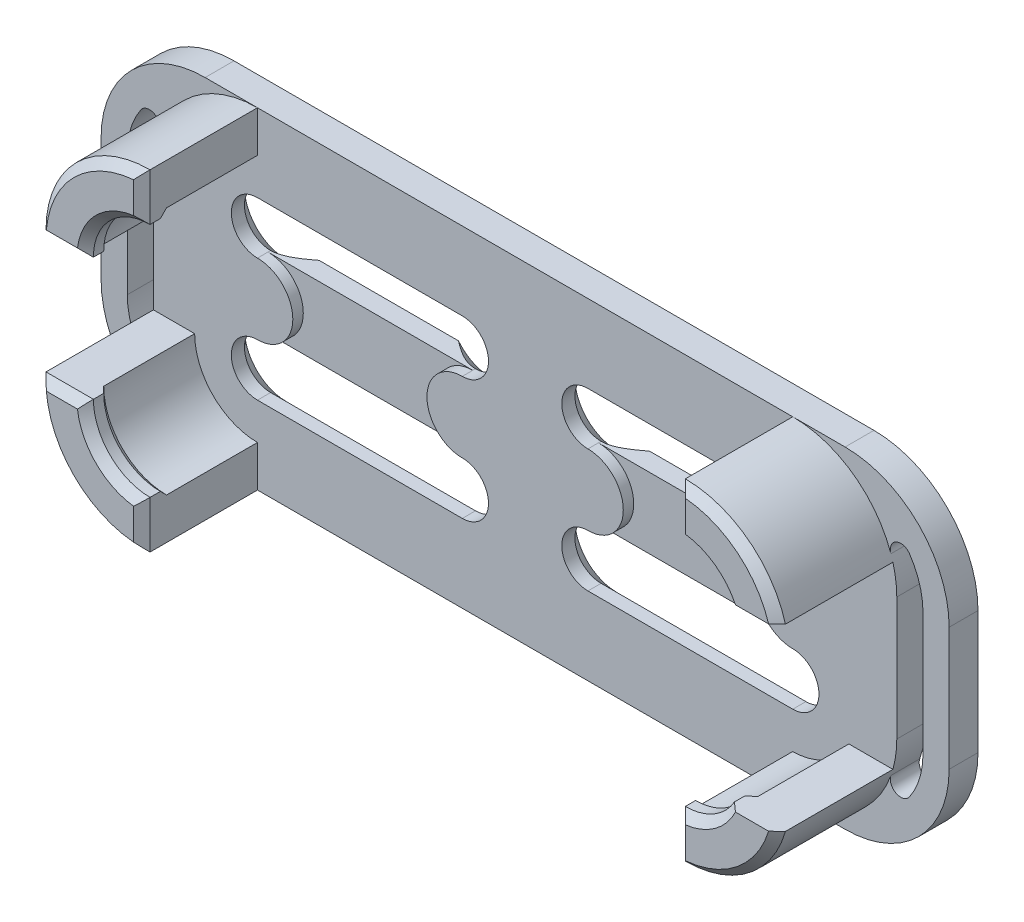
SolidWorks part; units mm, degrees
ref_plane "Front Plane" through (0, 0, 0) normal (0, 0, 1) x (1, 0, 0)
ref_plane "Top Plane" through (0, 0, 0) normal (0, 1, 0) x (1, 0, 0)
ref_plane "Right Plane" through (0, 0, 0) normal (1, 0, 0) x (0, 0, -1)
sketch "Sketch1" plane through (0, 0, 0) normal (0, 0, 1) x (1, 0, 0)
  line L0 (40.0844, 0) -> (-40.0844, 0) construction
  line L1 (0, -15.0813) -> (0, 15.0812) construction
  line L2 (40.0304, -8.8839) -> (60.6806, -8.8839)
  line L3 (60.6806, 8.8839) -> (40.0304, 8.8839)
  line L8 (-32.4644, -15.0813) -> (32.4644, -15.0812)
  line L9 (40.0844, -7.4612) -> (40.0844, 7.4612)
  line L10 (32.4644, 15.0812) -> (-32.4644, 15.0812)
  line L11 (-40.0844, 7.4612) -> (-40.0844, -7.4612)
  arc A8 (32.4644, -15.0812) -> (40.0844, -7.4612) centre (32.4644, -7.4612) ccw
  arc A9 (40.0844, 7.4612) -> (32.4644, 15.0812) centre (32.4644, 7.4612) ccw
  arc A10 (-32.4644, 15.0812) -> (-40.0844, 7.4612) centre (-32.4644, 7.4612) ccw
  arc A11 (-40.0844, -7.4612) -> (-32.4644, -15.0813) centre (-32.4644, -7.4612) ccw
  point P15 (0, 15.0812)
  point P18 (-40.0844, 0)
  point P22 (0, 0)
  point P25 (0, 0)
  point P27 (0, 0)
  point P29 (0, 0)
  dimension "D1" = 7.62
  dimension "D2" = 80.1688
  dimension "D3" = 30.1625
  dimension "D4" = 17.7678
sketch "Sketch2" plane through (0, 0, 0) normal (0, 0, 1) x (1, 0, 0)
  line L0 (-32.4644, 20.0813) -> (-32.4644, 15.0812)
  line L1 (-45.0844, 7.4612) -> (-40.0844, 7.4612)
  line L4 (-40.0844, 7.4612) -> (-40.0844, -7.4612)
  line L5 (32.4644, 15.0812) -> (-32.4644, 15.0813)
  line L6 (40.0844, -7.4612) -> (40.0844, 7.4612)
  line L7 (-32.4644, -15.0813) -> (32.4644, -15.0813)
  line L8 (-40.0844, 7.4612) -> (-40.0844, -7.4612) construction
  line L9 (32.4644, 15.0812) -> (-32.4644, 15.0813) construction
  line L10 (40.0844, -7.4612) -> (40.0844, 7.4612) construction
  line L11 (-32.4644, -15.0813) -> (32.4644, -15.0813) construction
  line L18 (32.4644, 20.0813) -> (32.4644, 15.0812)
  line L19 (45.0844, 7.4612) -> (40.0844, 7.4612)
  line L20 (-40.0844, -7.4612) -> (-45.0844, -7.4612)
  line L21 (-32.4644, -15.0813) -> (-32.4644, -20.0813)
  line L22 (32.4644, -20.0813) -> (32.4644, -15.0813)
  line L23 (40.0844, -7.4612) -> (45.0844, -7.4613)
  line L25 (32.4644, 20.0813) -> (-32.4644, 20.0813) construction
  line L26 (32.4644, 15.0812) -> (-32.4644, 15.0812) construction
  line L27 (45.0844, -7.4613) -> (45.0844, 7.4612) construction
  line L28 (40.0844, -7.4612) -> (40.0844, 7.4612) construction
  line L29 (-32.4644, -15.0813) -> (32.4644, -15.0813) construction
  line L30 (-32.4644, -20.0813) -> (32.4644, -20.0813) construction
  line L31 (-40.0844, 7.4612) -> (-40.0844, -7.4612) construction
  line L32 (-45.0844, 7.4612) -> (-45.0844, -7.4612) construction
  arc A0 (-40.0844, -7.4612) -> (-32.4644, -15.0813) centre (-32.4644, -7.4612) ccw
  arc A1 (32.4644, -15.0813) -> (40.0844, -7.4612) centre (32.4644, -7.4612) ccw
  arc A2 (40.0844, 7.4612) -> (32.4644, 15.0812) centre (32.4644, 7.4612) ccw
  arc A3 (-32.4644, 15.0812) -> (-40.0844, 7.4612) centre (-32.4644, 7.4612) ccw
  arc A4 (-32.4644, 15.0813) -> (-40.0844, 7.4612) centre (-32.4644, 7.4612) ccw
  arc A5 (40.0844, 7.4612) -> (32.4644, 15.0812) centre (32.4644, 7.4612) ccw
  arc A6 (32.4644, -15.0813) -> (40.0844, -7.4612) centre (32.4644, -7.4612) ccw
  arc A7 (-40.0844, -7.4612) -> (-32.4644, -15.0813) centre (-32.4644, -7.4612) ccw
  arc A8 (-32.4644, 15.0813) -> (-40.0844, 7.4612) centre (-32.4644, 7.4612) ccw construction
  arc A9 (40.0844, 7.4612) -> (32.4644, 15.0812) centre (32.4644, 7.4612) ccw construction
  arc A10 (32.4644, -15.0813) -> (40.0844, -7.4612) centre (32.4644, -7.4612) ccw construction
  arc A11 (-40.0844, -7.4612) -> (-32.4644, -15.0813) centre (-32.4644, -7.4612) ccw construction
  arc A12 (-45.0844, -7.4612) -> (-32.4644, -20.0813) centre (-32.4644, -7.4612) ccw
  arc A13 (32.4644, -20.0813) -> (45.0844, -7.4613) centre (32.4644, -7.4612) ccw
  arc A14 (45.0844, 7.4612) -> (32.4644, 20.0813) centre (32.4644, 7.4612) ccw
  arc A15 (-32.4644, 20.0813) -> (-45.0844, 7.4612) centre (-32.4644, 7.4612) ccw
  dimension "D1" = 0
  dimension "D3" = 5
extrude "Boss-Extrude1" add sketch "Sketch2" along normal blind 12.0331
sketch "Sketch3" plane through (0, 0, 0) normal (0, 0, -1) x (-1, 0, 0)
  line L0 (-45.0844, 7.4612) -> (-45.0844, -7.4612)
  line L1 (32.4644, -20.0813) -> (-32.4644, -20.0813)
  line L2 (45.0844, -7.4612) -> (45.0844, 7.4612)
  line L3 (32.4644, 20.0812) -> (-32.4644, 20.0813)
  line L4 (7.62, 7.4612) -> (32.4644, 7.4612) construction
  line L6 (7.62, 10.6362) -> (32.4644, 10.6362)
  line L7 (7.62, 4.2862) -> (32.4644, 4.2862)
  line L8 (-45.255, 0) -> (-50045.255, 0) construction
  line L9 (7.62, -7.4612) -> (32.4644, -7.4612) construction
  line L10 (7.62, -10.6362) -> (32.4644, -10.6362)
  line L11 (7.62, -4.2862) -> (32.4644, -4.2862)
  line L12 (35.6394, -7.4612) -> (40.0844, -7.4612) construction
  line L13 (4.445, -7.4612) -> (0, -7.4612) construction
  line L14 (0, -15.0813) -> (0, 15.0812) construction
  line L15 (0, 0) -> (0, 49794.0709) construction
  line L16 (-7.62, -7.4612) -> (-32.4644, -7.4612) construction
  line L17 (-7.62, -10.6362) -> (-32.4644, -10.6362)
  line L18 (-7.62, -4.2862) -> (-32.4644, -4.2862)
  line L19 (-7.62, 7.4612) -> (-32.4644, 7.4612) construction
  line L20 (-7.62, 10.6362) -> (-32.4644, 10.6362)
  line L21 (-7.62, 4.2862) -> (-32.4644, 4.2862)
  arc A0 (-45.0844, -7.4612) -> (-32.4644, -20.0813) centre (-32.4644, -7.4612) ccw construction
  arc A1 (32.4644, -20.0813) -> (45.0844, -7.4612) centre (32.4644, -7.4612) ccw construction
  arc A2 (45.0844, 7.4612) -> (32.4644, 20.0812) centre (32.4644, 7.4612) ccw construction
  arc A3 (-32.4644, 20.0813) -> (-45.0844, 7.4612) centre (-32.4644, 7.4612) ccw construction
  arc A4 (-45.0844, -7.4612) -> (-32.4644, -20.0813) centre (-32.4644, -7.4612) ccw
  arc A5 (32.4644, -20.0813) -> (45.0844, -7.4612) centre (32.4644, -7.4612) ccw
  arc A6 (45.0844, 7.4612) -> (32.4644, 20.0812) centre (32.4644, 7.4612) ccw
  arc A7 (-32.4644, 20.0813) -> (-45.0844, 7.4612) centre (-32.4644, 7.4612) ccw
  arc A8 (7.62, 10.6362) -> (7.62, 4.2862) centre (7.62, 7.4612) ccw
  arc A9 (32.4644, 4.2862) -> (32.4644, 10.6362) centre (32.4644, 7.4612) ccw
  arc A10 (7.62, -10.6362) -> (7.62, -4.2862) centre (7.62, -7.4612) cw
  arc A11 (32.4644, -4.2862) -> (32.4644, -10.6362) centre (32.4644, -7.4612) cw
  arc A12 (-7.62, -10.6362) -> (-7.62, -4.2862) centre (-7.62, -7.4612) ccw
  arc A13 (-32.4644, -4.2862) -> (-32.4644, -10.6362) centre (-32.4644, -7.4612) ccw
  arc A14 (-7.62, 10.6362) -> (-7.62, 4.2862) centre (-7.62, 7.4612) cw
  arc A15 (-32.4644, 4.2862) -> (-32.4644, 10.6362) centre (-32.4644, 7.4612) cw
  point P13 (20.0422, 7.4612)
  point P22 (-45.0844, 0)
  point P25 (20.0422, -7.4612)
  point P37 (0, 0)
  point P40 (-20.0422, -7.4612)
  point P47 (-20.0422, 7.4612)
  dimension "D1" = 6.35
extrude "Boss-Extrude2" add sketch "Sketch3" along normal blind 3.5
sketch "Sketch5" plane through (0, 0, 12.0331) normal (0, 0, 1) x (1, 0, 0)
  line L0 (0, 0) -> (0, 49206.6914) construction
  line L1 (40.0844, 0) -> (-40.0844, 0) construction
  line L2 (-32.4644, 15.0813) -> (-32.4644, 20.0812)
  line L3 (-45.0844, 7.4612) -> (-40.0844, 7.4612)
  line L4 (-32.4644, 14.3313) -> (-32.4644, 20.0812)
  line L5 (-45.0844, 7.4612) -> (-39.3344, 7.4612)
  line L7 (0, 0) -> (49995.6844, 0) construction
  line L15 (32.4644, 14.3313) -> (32.4644, 20.0812)
  line L16 (45.0844, 7.4612) -> (39.3344, 7.4612)
  line L17 (45.0844, -7.4613) -> (39.3344, -7.4613)
  line L18 (32.4644, -14.3313) -> (32.4644, -20.0813)
  line L19 (-45.0844, -7.4613) -> (-39.3344, -7.4613)
  line L20 (-32.4644, -14.3313) -> (-32.4644, -20.0813)
  arc A0 (-32.4644, 14.3313) -> (-39.3344, 7.4612) centre (-32.4644, 7.4612) ccw
  arc A2 (-32.4644, 15.0813) -> (-40.0844, 7.4612) centre (-32.4644, 7.4612) ccw
  arc A3 (-32.4644, 20.0812) -> (-45.0844, 7.4612) centre (-32.4644, 7.4612) ccw
  arc A4 (-32.4644, 15.0813) -> (-40.0844, 7.4612) centre (-32.4644, 7.4612) ccw construction
  arc A5 (-32.4644, 20.0812) -> (-45.0844, 7.4612) centre (-32.4644, 7.4612) ccw
  arc A11 (32.4644, 20.0812) -> (45.0844, 7.4612) centre (32.4644, 7.4612) cw
  arc A12 (32.4644, 14.3313) -> (39.3344, 7.4612) centre (32.4644, 7.4612) cw
  arc A13 (-32.4644, -15.0813) -> (-40.0844, -7.4613) centre (-32.4644, -7.4613) cw construction
  arc A14 (32.4644, -14.3313) -> (39.3344, -7.4613) centre (32.4644, -7.4613) ccw
  arc A15 (32.4644, -20.0813) -> (45.0844, -7.4613) centre (32.4644, -7.4613) ccw
  arc A16 (-32.4644, -20.0813) -> (-45.0844, -7.4613) centre (-32.4644, -7.4613) cw
  arc A17 (-32.4644, -14.3313) -> (-39.3344, -7.4613) centre (-32.4644, -7.4613) cw
  point P13 (0, 0)
  dimension "D1" = 0
  dimension "D2" = 0.75
extrude "Boss-Extrude3" add sketch "Sketch5" along normal blind 2
sketch "Sketch4" plane through (0, 0, 0) normal (0, 0, 1) x (1, 0, 0)
  line L0 (0, 0) -> (0, 50000) construction
  line L1 (-32.4644, -4.2862) -> (-7.62, -4.2862)
  line L2 (-32.4644, -4.2862) -> (-32.4644, 4.2862) construction
  line L3 (-32.4644, 4.2862) -> (-7.62, 4.2862)
  line L4 (-7.62, -4.2862) -> (-7.62, 4.2862) construction
  line L5 (-32.4644, -4.2862) -> (-7.62, 4.2862) construction
  line L6 (-32.4644, 4.2862) -> (-7.62, -4.2862) construction
  line L7 (-20.0422, 0) -> (-20.0422, 50000) construction
  arc A0 (-7.62, -10.6362) -> (-7.62, -4.2862) centre (-7.62, -7.4612) ccw construction
  arc A1 (-7.62, 4.2862) -> (-7.62, 10.6362) centre (-7.62, 7.4612) ccw construction
  arc A2 (-32.4644, -4.2862) -> (-32.4644, -10.6362) centre (-32.4644, -7.4612) ccw construction
  arc A3 (-32.4644, 10.6362) -> (-32.4644, 4.2862) centre (-32.4644, 7.4612) ccw construction
  arc A4 (-7.62, -10.6362) -> (-7.62, -4.2862) centre (-7.62, -7.4612) ccw construction
  arc A5 (-7.62, 4.2862) -> (-7.62, 10.6362) centre (-7.62, 7.4612) ccw construction
  arc A6 (-32.4644, -4.2862) -> (-32.4644, -10.6362) centre (-32.4644, -7.4612) ccw construction
  arc A7 (-32.4644, 10.6362) -> (-32.4644, 4.2862) centre (-32.4644, 7.4612) ccw construction
  arc A8 (-32.4644, 4.2862) -> (-32.4644, -4.2862) centre (-32.4644, 0) cw
  arc A10 (-7.62, 4.2862) -> (-7.62, -4.2862) centre (-7.62, 0) ccw
  point P0 (0, 0)
  point P20 (-20.0422, 0)
extrude "Cut-Extrude1" cut sketch "Sketch4" against normal blind 1.27
chamfer "Chamfer1" distance 1 angle 45 20 edges at (42.2094, 7.4612, 14.0331) (37.3222, 12.3191, 14.0331) (32.4644, 17.2063, 14.0331) (41.3881, 16.3849, 14.0331) (42.2094, -7.4613, 14.0331) (41.3881, -16.3849, 14.0331) (32.4644, -17.2063, 14.0331) (37.3222, -12.3191, 14.0331) (-32.4644, 17.2063, 14.0331) (-37.3222, 12.3191, 14.0331) (-42.2094, 7.4612, 14.0331) (-41.3881, 16.3849, 14.0331) (-42.2094, -7.4613, 14.0331) (-37.3222, -12.3191, 14.0331) (-32.4644, -17.2063, 14.0331) (-41.3881, -16.3849, 14.0331) (-37.8525, -12.8494, 12.0331) (37.8525, -12.8494, 12.0331) (37.8525, 12.8494, 12.0331) (-37.8525, 12.8494, 12.0331)
sketch "Sketch7" plane through (0, 0, 0) normal (0, 0, 1) x (1, 0, 0)
  line L0 (40.0304, -8.8839) -> (60.6806, -8.8839) construction
  line L1 (60.6806, 8.8839) -> (40.0304, 8.8839) construction
  line L2 (40.0304, -8.8839) -> (60.6806, -8.8839) construction
  line L3 (60.6806, 8.8839) -> (40.0304, 8.8839) construction
  line L4 (60.6806, 10.8839) -> (38.4211, 10.8839)
  line L5 (38.4211, -10.8839) -> (60.6806, -10.8839)
  line L6 (60.6806, 10.8839) -> (40.0304, 10.8839) construction
  line L7 (40.0304, -10.8839) -> (60.6806, -10.8839) construction
  line L8 (45.0844, 7.4612) -> (39.3344, 7.4612) construction
  line L9 (39.3344, -7.4613) -> (45.0844, -7.4612) construction
  line L10 (45.0844, 7.4612) -> (39.3344, 7.4612)
  line L11 (39.3344, -7.4613) -> (45.0844, -7.4612)
  arc A0 (32.4644, -14.3313) -> (39.3344, -7.4613) centre (32.4644, -7.4613) ccw construction
  arc A1 (39.3344, 7.4612) -> (32.4644, 14.3313) centre (32.4644, 7.4612) ccw construction
  arc A2 (38.4211, -10.8839) -> (39.3344, -7.4613) centre (32.4644, -7.4613) ccw
  arc A3 (39.3344, 7.4612) -> (38.4211, 10.8839) centre (32.4644, 7.4612) ccw
  arc A4 (32.4644, -20.0813) -> (45.0844, -7.4612) centre (32.4644, -7.4612) ccw construction
  arc A5 (45.0844, 7.4612) -> (32.4644, 20.0813) centre (32.4644, 7.4612) ccw construction
  arc A6 (44.6114, -10.8839) -> (45.0844, -7.4612) centre (32.4644, -7.4612) ccw
  arc A7 (45.0844, 7.4612) -> (44.6114, 10.8839) centre (32.4644, 7.4612) ccw
  line M12 (45.0844, 7.4612) -> (40.0844, 7.4612)
  arc M13 (40.0844, 7.4612) -> (32.4644, 15.0812) centre (32.4644, 7.4612) ccw
  arc M25 (32.4644, -15.0813) -> (40.0844, -7.4612) centre (32.4644, -7.4612) ccw
  line M26 (40.0844, -7.4612) -> (45.0844, -7.4612)
  dimension "D1" = 2
extrude "Cut-Extrude2" cut sketch "Sketch7" along normal through all contours L5 A6 M26 M25 | A7 L4 M12 M13 | A3 L10 L4 M13 | A2 L5 L11 M25
sketch "Sketch8" plane through (0, 0, -3.5) normal (0, 0, -1) x (-1, 0, 0)
  line L0 (45.0844, -7.4612) -> (45.0844, 7.4612) construction
  line L1 (45.0844, -7.4612) -> (45.0844, 7.4612)
  line L11 (0, 0) -> (0, -49857.9419) construction
  line L12 (-40.0844, 0) -> (40.0844, 0) construction
  line L13 (51.4344, -7.4612) -> (51.4344, 7.4612)
  line L14 (-51.4344, 7.4612) -> (-51.4344, -7.4613)
  line L16 (-32.4644, -20.0813) -> (-38.8144, -20.0813)
  line L22 (32.4644, 20.0812) -> (38.8144, 20.0812)
  line L23 (38.8144, -20.0813) -> (32.4644, -20.0813)
  line L24 (48.2594, -7.4613) -> (48.2594, 7.4612)
  line L25 (-45.0844, 7.4612) -> (-45.0844, -7.4612) construction
  line L26 (-45.0844, 7.4612) -> (-45.0844, -7.4612) construction
  line L27 (-32.4644, 20.0813) -> (-38.8144, 20.0813)
  line L28 (-48.2594, 7.4612) -> (-48.2594, -7.4613)
  line L29 (-48.2594, 7.4612) -> (-48.2594, -7.4613) construction
  arc A0 (45.0844, 7.4612) -> (32.4644, 20.0812) centre (32.4644, 7.4612) ccw construction
  arc A1 (32.4644, -20.0813) -> (45.0844, -7.4612) centre (32.4644, -7.4612) ccw construction
  arc A2 (45.0844, 7.4612) -> (32.4644, 20.0812) centre (32.4644, 7.4612) ccw
  arc A3 (32.4644, -20.0813) -> (45.0844, -7.4612) centre (32.4644, -7.4612) ccw
  arc A12 (51.4344, 7.4612) -> (38.8144, 20.0812) centre (38.8144, 7.4612) ccw
  arc A13 (38.8144, -20.0813) -> (51.4344, -7.4612) centre (38.8144, -7.4612) ccw
  arc A15 (41.1556, -16.6115) -> (48.2594, -7.4613) centre (38.8144, -7.4612) ccw
  arc A16 (48.2594, 7.4612) -> (41.1556, 16.6115) centre (38.8144, 7.4612) ccw
  arc A22 (48.2594, 7.4612) -> (38.8144, 16.9062) centre (38.8144, 7.4612) ccw construction
  arc A24 (38.8144, -16.9062) -> (48.2594, -7.4613) centre (38.8144, -7.4612) ccw construction
  arc A25 (-32.4644, 20.0813) -> (-45.0844, 7.4612) centre (-32.4644, 7.4612) ccw construction
  arc A26 (-45.0844, -7.4612) -> (-32.4644, -20.0813) centre (-32.4644, -7.4612) ccw construction
  arc A27 (-32.4644, 20.0813) -> (-41.1556, 16.6115) centre (-32.4644, 7.4612) ccw
  arc A28 (-41.1556, -16.6115) -> (-32.4644, -20.0813) centre (-32.4644, -7.4612) ccw
  arc A29 (-38.8144, 20.0813) -> (-51.4344, 7.4612) centre (-38.8144, 7.4612) ccw
  arc A30 (-51.4344, -7.4613) -> (-38.8144, -20.0813) centre (-38.8144, -7.4613) ccw
  arc A31 (-48.2594, -7.4613) -> (-41.1556, -16.6115) centre (-38.8144, -7.4613) ccw
  arc A32 (-41.1556, 16.6115) -> (-48.2594, 7.4612) centre (-38.8144, 7.4612) ccw
  point P37 (0, 0)
  point P41 (-40.0844, -16.9063)
  point P43 (-40.0844, 16.9062)
  point P47 (-49.5294, -7.4625)
  point P50 (0, 0)
  point P51 (0, 0)
  point P52 (-49.5294, 7.4612)
  point P53 (0, 0)
  point P54 (-49.5294, 7.3574)
  point P55 (0, 0)
  arc M41 (-45.0844, -7.4612) -> (-32.4644, -20.0813) centre (-32.4644, -7.4612) ccw
  arc M43 (32.4644, -20.0813) -> (45.0844, -7.4612) centre (32.4644, -7.4612) ccw
  arc M47 (-32.4644, 20.0813) -> (-45.0844, 7.4612) centre (-32.4644, 7.4612) ccw
  dimension "D4" = 2
  dimension "D2" = 3.175
  dimension "D3" = 6.35
  dimension "D5" = 6.35
  dimension "D6" = 3.175
  dimension "D1" = 2
extrude "Boss-Extrude4" add sketch "Sketch8" against normal up to surface (3.5 mm away) contours A32 L27 A29 L14 A30 L16 A31 L28 M47 M41 | A16 L24 A15 L23 A13 L13 A12 L22 A2 M43 up to face at (4.7704, 0, 0)
fillet "Fillet1" radius 1.27 4 edges at (-41.1556, 16.6115, -1.75) (-41.1556, -16.6115, -1.75) (41.1556, 16.6115, -1.75) (41.1556, -16.6115, -1.75)
mirror "Mirror3" about plane through (0, 0, 0) normal (1, 0, 0) of "Cut-Extrude1"
chamfer "Chamfer2" distance 1.905 angle 45 4 edges at (-20.0422, -10.6362, -3.5) (-20.0422, 10.6362, -3.5) (20.0422, 10.6362, -3.5) (20.0422, -10.6362, -3.5)
